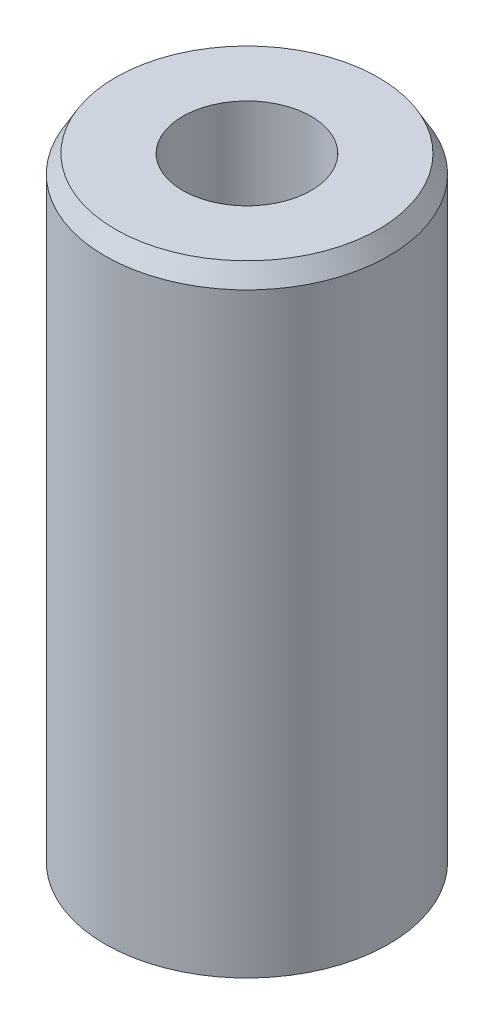
SolidWorks part; units mm, degrees
ref_plane "Front Plane" through (0, 0, 0) normal (0, 0, 1) x (1, 0, 0)
ref_plane "Top Plane" through (0, 0, 0) normal (0, 1, 0) x (1, 0, 0)
ref_plane "Right Plane" through (0, 0, 0) normal (1, 0, 0) x (0, 0, -1)
sketch "Sketch1" plane through (0, 0, 0) normal (0, 1, 0) x (1, 0, 0)
  circle A0 centre (0, 0) radius 10
  dimension "SHAFT_OD" = 20
extrude "Boss-Extrude1" add sketch "Sketch1" along normal blind 43.9896
sketch "Sketch2" plane through (0, 0, 0) normal (0, 1, 0) x (1, 0, 0)
  circle A0 centre (0, 0) radius 4.5301
  dimension "BORE_D" = 9.0602
extrude "Cut-Extrude1" cut sketch "Sketch2" along normal through all
chamfer "Chamfer1" distance 1.2619 angle 30 2 edges at (0, 43.9896, 10) (0, 0, 10) first distance on face at (0, 43.9896, 10) first distance on face at (0, 0, 4.5301)
